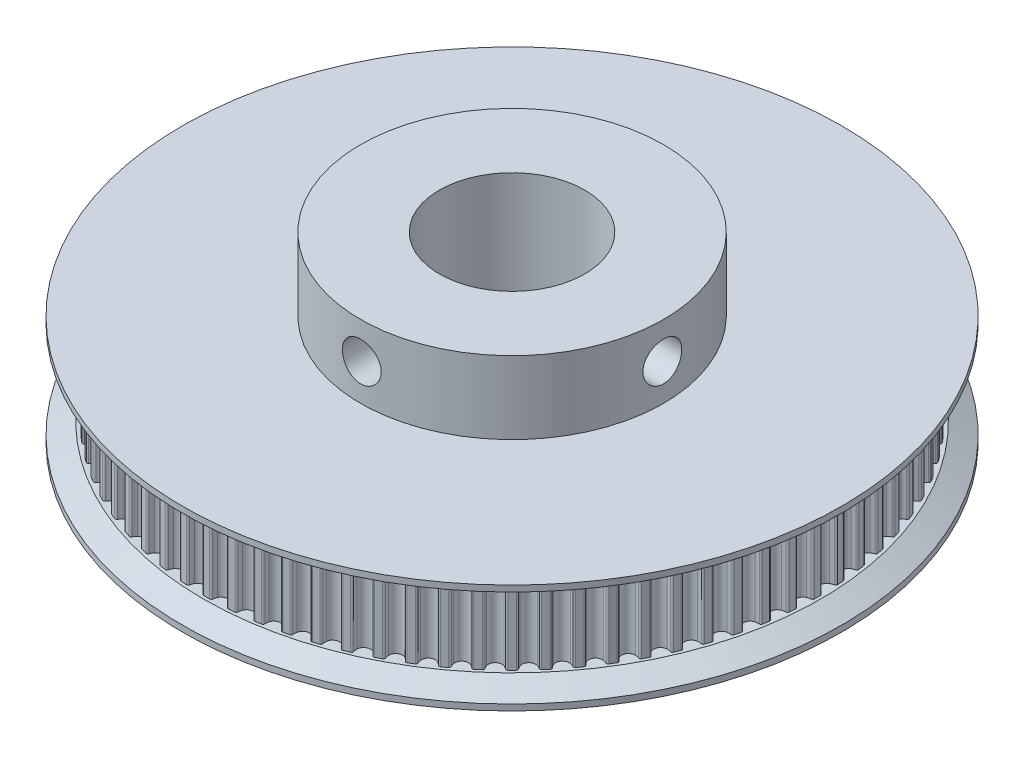
SolidWorks part; units mm, degrees
ref_plane "Front" through (0, 0, 0) normal (0, 0, 1) x (1, 0, 0)
ref_plane "Top" through (0, 0, 0) normal (0, 1, 0) x (1, 0, 0)
ref_plane "Right" through (0, 0, 0) normal (1, 0, 0) x (0, 0, -1)
sketch "Sketch1" plane through (0, 0, 0) normal (0, 1, 0) x (1, 0, 0)
  line L0 (0, 0) -> (0, 25.4648) construction
  line L1 (0, 25.2108) -> (0, 25.8408)
  line L2 (0, 0) -> (0.9997, 25.4452) construction
  line L3 (1.978, 25.1331) -> (2.0274, 25.7611)
  line L4 (1.3894, 25.1757) -> (1.4033, 25.4261) construction
  arc A0 (0.2468, 25.2096) -> (0.3946, 25.0747) centre (0.2453, 25.0596) cw
  arc A1 (0.3946, 25.0747) -> (0.4741, 24.773) centre (1.3894, 25.1757) ccw
  circle A2 centre (0, 0) radius 25.4648 construction
  arc A3 (0.2468, 25.2096) -> (0, 25.2108) centre (0, 0) ccw
  arc A4 (0.9603, 24.4419) -> (0, 24.4608) centre (0, 0) ccw construction
  arc A5 (0.4741, 24.773) -> (1.471, 24.7339) centre (0.9821, 24.9965) ccw
  arc A6 (1.3894, 25.1757) -> (0.9899, 25.1946) centre (0, 0) ccw construction
  arc A7 (0, 25.8408) -> (2.0274, 25.7611) centre (0, 0) cw
  arc A8 (1.574, 25.0284) -> (1.471, 24.7339) centre (0.5901, 25.2071) cw
  arc A9 (1.7319, 25.1512) -> (1.574, 25.0284) centre (1.7216, 25.0016) ccw
  arc A10 (1.7319, 25.1512) -> (1.978, 25.1331) centre (0, 0) cw
  dimension "D1" = 0.15
  dimension "D4" = 50.9296
  dimension "D5" = 1
  dimension "D7" = 0.555
  dimension "D3" = 2.25
  dimension "D8" = 0.75
  dimension "D6" = 0.254
  dimension "D2" = 0.4
  dimension "D9" = 1.38
  dimension "D11" = 0.404
  dimension "D12" = 0.2508
  dimension "D10" = 0.909
sketch "Sketch2" plane through (0, 0, 0) normal (0, 1, 0) x (1, 0, 0)
  circle A0 centre (0, 0) radius 25.4648 construction
  circle A1 centre (0, 0) radius 25.4648
  circle A2 centre (0, 0) radius 6
  dimension "D1" = 12
extrude "Boss-Extrude1" add sketch "Sketch2" along normal mid plane 6
sketch "Sketch6" plane through (0, 0, 0) normal (0, 1, 0) x (1, 0, 0)
  line L0 (0, 25.2008) -> (0, 25.8408)
  line L1 (1.9772, 25.1231) -> (2.0274, 25.7611)
  arc A7 (2.0274, 25.7611) -> (0, 25.8408) centre (0, 0) ccw construction
  arc A8 (2.0274, 25.7611) -> (0, 25.8408) centre (0, 0) ccw
  arc A14 (1.7312, 25.1413) -> (1.5838, 25.0266) centre (1.7216, 25.0016) ccw
  arc A15 (1.4798, 24.7291) -> (1.5838, 25.0266) centre (0.5901, 25.2071) ccw
  arc A16 (0.4649, 24.769) -> (1.4798, 24.7291) centre (0.9821, 24.9965) ccw
  arc A17 (0.3846, 25.0737) -> (0.4649, 24.769) centre (1.3894, 25.1757) ccw
  arc A18 (0.3846, 25.0737) -> (0.2467, 25.1996) centre (0.2453, 25.0596) ccw
  arc A19 (0.2467, 25.1996) -> (0, 25.2008) centre (0, 0) ccw
  arc A20 (1.9772, 25.1231) -> (1.7312, 25.1413) centre (0, 0) ccw
  arc A21 (1.7312, 25.1413) -> (1.5838, 25.0266) centre (1.7216, 25.0016) ccw
  arc A22 (1.4798, 24.7291) -> (1.5838, 25.0266) centre (0.5901, 25.2071) ccw
  arc A23 (0.4649, 24.769) -> (1.4798, 24.7291) centre (0.9821, 24.9965) ccw
  arc A24 (0.3846, 25.0737) -> (0.4649, 24.769) centre (1.3894, 25.1757) ccw
  arc A25 (0.3846, 25.0737) -> (0.2467, 25.1996) centre (0.2453, 25.0596) ccw
  arc A26 (0.2467, 25.1996) -> (0, 25.2008) centre (0, 0) ccw
  arc A27 (1.9772, 25.1231) -> (1.7312, 25.1413) centre (0, 0) ccw
extrude "Cut-Extrude3" cut sketch "Sketch6" against normal through all both and the other way through all
pattern_circular "CirPattern3" count 80 over 360 about axis through (0, 3, 0) along (0, -1, 0) of "Cut-Extrude3"
sketch "Sketch3" plane through (0, 0, 0) normal (0, 0, 1) x (1, 0, 0)
  line L0 (0, 0) -> (0, 9.5108) construction
  line L1 (-25.4648, 3) -> (-27.1968, 4)
  line L2 (-27.1968, 4) -> (-27.1968, 4.5)
  line L3 (-27.1968, 4.5) -> (-6, 4.5)
  line L4 (-6, 4.5) -> (-6, 3)
  line L5 (-6, 3) -> (-25.4648, 3)
  line L6 (6, 3) -> (-6, 3) construction
  dimension "D4" = 50.9296
  dimension "D1" = 1.5
  dimension "D2" = 0.5
  dimension "D3" = 30
revolve "Revolve1" add sketch "Sketch3" angle 360 about L0
mirror "Mirror1" about plane through (0, 0, 0) normal (0, 1, 0) of "Revolve1"
sketch "Sketch4" plane through (0, 0, 0) normal (0, 0, 1) x (1, 0, 0)
  line L0 (0, 0) -> (0, 14.0175) construction
  line L1 (27.1968, 4.5) -> (-27.1968, 4.5) construction
  line L2 (-6, 4.5) -> (-12.5, 4.5)
  line L3 (-6, 4.5) -> (-6, 10.5)
  line L4 (-6, 10.5) -> (-12.5, 10.5)
  line L5 (-12.5, 4.5) -> (-12.5, 10.5)
  dimension "D2" = 6
  dimension "D1" = 6.5
revolve "Revolve2" add sketch "Sketch4" angle 360 about L0
sketch "Sketch5" plane through (0, 0, 0) normal (0, 0, 1) x (1, 0, 0)
  line L1 (0, 4.5) -> (0, 10.5) construction
  line L2 (12.5, 10.5) -> (-12.5, 10.5) construction
  line L7 (-12.5, 10.5) -> (-12.5, 4.5) construction
  line L8 (-12.5, 10.5) -> (-12.5, 4.5) construction
  circle A0 centre (0, 7.5) radius 1.6
  dimension "D1" = 3.2
extrude "Cut-Extrude2" cut sketch "Sketch5" along normal through all
pattern_circular "CirPattern2" count 2 over 90 about axis through (0, 3, 0) along (0, -1, 0) of "Cut-Extrude2" reverse direction yes
equation "\"belt-step\"= 2"
equation "\"pulley-teeth\"= 80"
equation "\"pulley-dia\"= ( \"belt-step\" * \"pulley-teeth\" ) / Pi"
equation "\"D3@Sketch1\"=(360/\"pulley-teeth\")/2"
equation "\"D4@Sketch1\"=\"pulley-dia\""
equation "\"bore-dia\"= 12"
equation "\"belt-thick\"= 6"
equation "\"D4@Sketch3\"=\"pulley-dia\""
equation "\"D1@Sketch2\"=\"bore-dia\""
equation "\"D1@Boss-Extrude1\"=\"belt-thick\""
equation "\"teeth-offset\"= 0.01"
equation "\"D1@Sketch6\"=\"teeth-offset\""
equation "\"D1@CirPattern3\"=\"pulley-teeth\""
equation "\"flange-wall\"= 6.5"
equation "\"D1@Sketch4\"=\"flange-wall\""
equation "\"flange-h\"= 6"
equation "\"screw-dia\"= 3.2"
equation "\"D2@Sketch4\"=\"flange-h\""
equation "\"D1@Sketch5\"=\"screw-dia\""
equation "\"D10@Sketch1\"=(0.4/(Pi*(\"pulley-dia\"-(2*\"D12@Sketch1\"))))*360"
